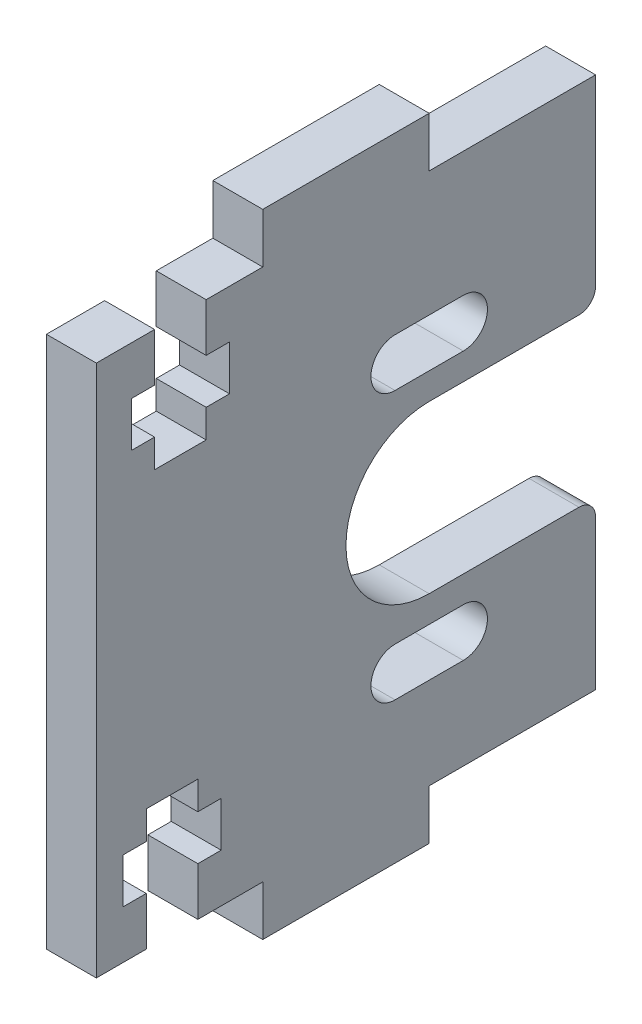
SolidWorks part; units mm, degrees
ref_plane "Front Plane" through (0, 0, 0) normal (0, 0, 1) x (1, 0, 0)
ref_plane "Top Plane" through (0, 0, 0) normal (0, 1, 0) x (1, 0, 0)
ref_plane "Right Plane" through (0, 0, 0) normal (1, 0, 0) x (0, 0, -1)
sketch "Sketch1" plane through (0, 0, 0) normal (1, 0, 0) x (0, 0, -1)
  line L1 (0, 0) -> (30, 0)
  line L2 (0, 0) -> (0, 38)
  line L3 (0, 38) -> (30, 38)
  line L4 (30, 0) -> (30, 38)
  dimension "D1" = 30
  dimension "D2" = 38
extrude "Boss-Extrude1" add sketch "Sketch1" along normal blind 3
sketch "Sketch2" plane through (3, 0, 0) normal (1, 0, 0) x (0, 0, -1)
  line L0 (30, 0) -> (30, 38) construction
  line L3 (30, 38) -> (0, 38) construction
  circle A0 centre (20, 18) radius 5
  dimension "D1" = 10
  dimension "D2" = 10
  dimension "D3" = 20
extrude "Cut-Extrude1" cut sketch "Sketch2" against normal blind 3
sketch "Sketch6" plane through (3, 0, 0) normal (1, 0, 0) x (0, 0, -1)
  line L1 (0, 0) -> (10, 0)
  line L2 (0, 0) -> (0, 3)
  line L3 (0, 3) -> (10, 3)
  line L4 (10, 0) -> (10, 3)
  line L5 (30, 0) -> (20, 0)
  line L6 (30, 0) -> (30, 3)
  line L7 (30, 3) -> (20, 3)
  line L8 (20, 0) -> (20, 3)
  dimension "D1" = 3
  dimension "D2" = 3
  dimension "D3" = 10
  dimension "D4" = 10
extrude "Cut-Extrude2" cut sketch "Sketch6" against normal blind 3
sketch "Sketch7" plane through (3, 0, 0) normal (1, 0, 0) x (0, 0, -1)
  line L0 (3, 3) -> (3, 5.9)
  line L1 (3, 5.9) -> (1.6, 5.9)
  line L2 (1.6, 5.9) -> (1.6, 8.6)
  line L3 (1.6, 8.6) -> (3, 8.6)
  line L4 (3, 8.6) -> (3, 10.3)
  line L5 (3, 10.3) -> (6.1, 10.3)
  line L6 (6.1, 10.3) -> (6.1, 8.6)
  line L7 (6.1, 8.6) -> (7.5, 8.6)
  line L8 (7.5, 8.6) -> (7.5, 5.9)
  line L9 (7.5, 5.9) -> (6.1, 5.9)
  line L10 (6.1, 5.9) -> (6.1, 3)
  line L11 (6.1, 3) -> (3, 3)
  line L24 (10, 3) -> (0, 3) construction
  line L25 (0, 38) -> (0, 3) construction
  dimension "D1" = 0
  dimension "D2" = 3
  dimension "D3" = 3.1
  dimension "D4" = 1.4
  dimension "D5" = 2.7
  dimension "D6" = 2.9
  dimension "D7" = 1.7
extrude "Cut-Extrude3" cut sketch "Sketch7" against normal blind 3
sketch "Sketch9" plane through (3, 0, 0) normal (1, 0, 0) x (0, 0, -1)
  line L1 (0, 38) -> (10, 38)
  line L2 (0, 38) -> (0, 35)
  line L3 (0, 35) -> (10, 35)
  line L4 (10, 38) -> (10, 35)
  line L5 (30, 38) -> (20, 38)
  line L6 (30, 38) -> (30, 35)
  line L7 (30, 35) -> (20, 35)
  line L8 (20, 38) -> (20, 35)
  dimension "D1" = 3
  dimension "D2" = 3
  dimension "D3" = 10
  dimension "D4" = 10
extrude "Cut-Extrude5" cut sketch "Sketch9" against normal blind 10
sketch "Sketch12" plane through (3, 0, 0) normal (1, 0, 0) x (0, 0, -1)
  line L0 (6.6, 35) -> (6.6, 32.1)
  line L1 (6.6, 32.1) -> (8, 32.1)
  line L2 (8, 32.1) -> (8, 29.4)
  line L3 (8, 29.4) -> (6.6, 29.4)
  line L4 (6.6, 29.4) -> (6.6, 27.7)
  line L5 (6.6, 27.7) -> (3.5, 27.7)
  line L6 (3.5, 27.7) -> (3.5, 29.4)
  line L7 (3.5, 29.4) -> (2.1, 29.4)
  line L8 (2.1, 29.4) -> (2.1, 32.1)
  line L9 (2.1, 32.1) -> (3.5, 32.1)
  line L10 (3.5, 32.1) -> (3.5, 35)
  line L11 (3.5, 35) -> (6.6, 35)
  line L12 (0, 35) -> (10, 35) construction
  line L13 (0, 35) -> (0, 3) construction
  dimension "D1" = 2.9
  dimension "D2" = 2.7
  dimension "D3" = 1.7
  dimension "D4" = 3.1
  dimension "D5" = 1.4
  dimension "D6" = 0
  dimension "D7" = 2.9
  dimension "D8" = 3.5
  dimension "D9" = 1.7
extrude "Cut-Extrude6" cut sketch "Sketch12" against normal blind 10
hole_wizard "M2.5 Clearance Slot1" positions "Sketch15" profile "Sketch16" size "M2.5" standard "ANSI Metric" slot yes
sketch "Sketch15" plane through (3, 0, 0) normal (1, 0, 0) x (0, 0, -1)
  line L0 (19, 18) -> (20, 18) construction
  line L1 (23.5, 26.05) -> (16.5, 26.05) construction
  circle A0 centre (20, 18) radius 5 construction
  point P0 (20, 26.05)
  point P2 (20, 9.95)
  point P16 (0, 0)
  point P17 (0, 0)
  point P18 (0, 0)
  dimension "D1" = 16.1
  dimension "D2" = 8.05
  dimension "D3" = 7
sketch "Sketch16" plane through (3, 26.05, -20) normal (0, 1, 0) x (0, 0, -1)
  line L0 (0, 0) -> (0, 3.8712)
  line L1 (0, 3.8712) -> (1.45, 3)
  line L2 (1.45, 3) -> (1.45, 0)
  line L5 (1.45, 0) -> (0, 0)
  line L10 (0, 3.8712) -> (-1.45, 3) construction
  line L11 (0, -6.35) -> (0, 107.95) construction
  dimension "Hole Dia." = 2.9
  dimension "Hole Depth" = 3
  dimension "Drill Angle" = 118
sketch "Sketch17" plane through (3, 0, 0) normal (1, 0, 0) x (0, 0, -1)
  line L5 (30, 3) -> (30, 35) construction
  line L6 (20, 23) -> (30, 23)
  line L7 (20, 23) -> (20, 13)
  line L8 (20, 13) -> (30, 13)
  line L9 (30, 23) -> (30, 13)
  circle A1 centre (20, 18) radius 5 construction
extrude "Cut-Extrude7" cut sketch "Sketch17" against normal blind 10
fillet "Fillet1" radius 1 2 edges at (1.5, 13, -30) (1.5, 23, -30)
